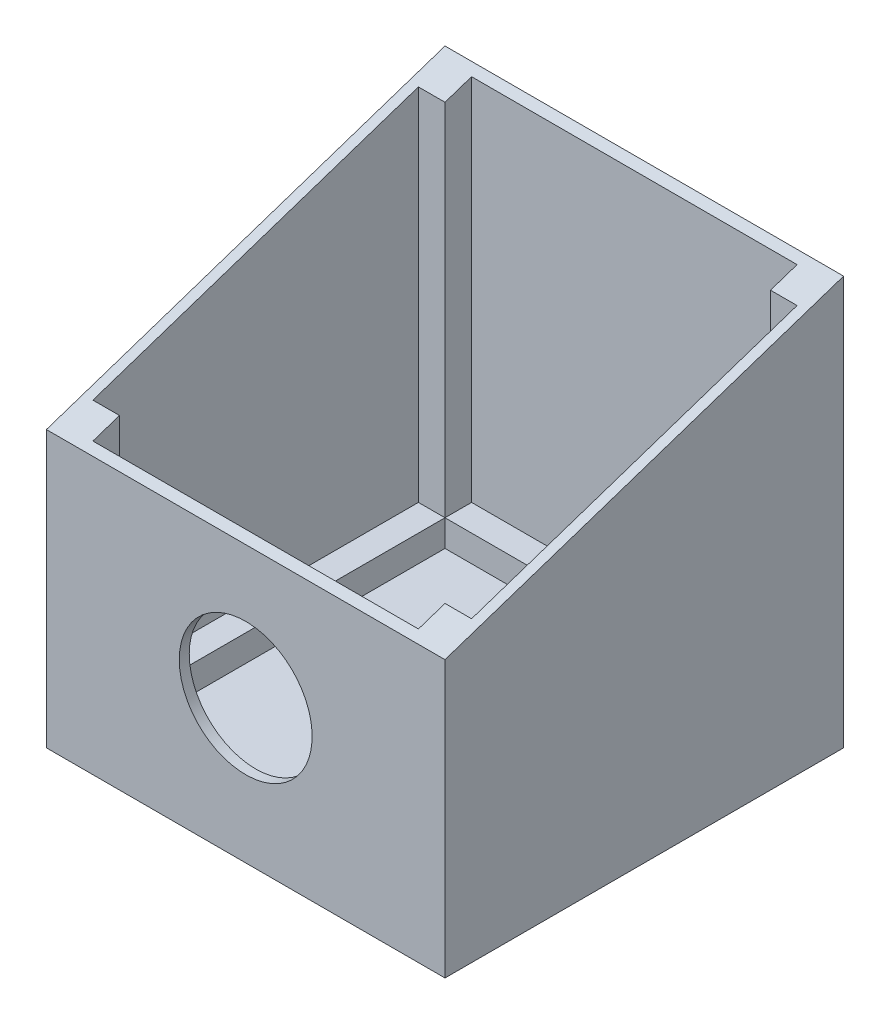
SolidWorks part; units mm, degrees
ref_plane "Alzado" through (0, 0, 0) normal (0, 0, 1) x (1, 0, 0)
ref_plane "Planta" through (0, 0, 0) normal (0, 1, 0) x (1, 0, 0)
ref_plane "Vista lateral" through (0, 0, 0) normal (1, 0, 0) x (0, 0, -1)
sketch "Croquis1" plane through (0, 0, 0) normal (0, 1, 0) x (1, 0, 0)
  line L0 (-3, 117) -> (117, 117)
  line L1 (8, 0) -> (106, 0)
  line L2 (0, 8) -> (0, 106)
  line L3 (8, 114) -> (106, 114)
  line L4 (114, 8) -> (114, 106)
  line L5 (117, -3) -> (117, 117)
  line L6 (-3, -3) -> (117, -3)
  line L7 (-3, -3) -> (-3, 117)
  line L8 (0, 114) -> (114, 114) construction
  line L9 (0, 0) -> (0, 114) construction
  line L10 (114, 0) -> (114, 114) construction
  line L11 (0, 106) -> (8, 106)
  line L12 (8, 114) -> (8, 106)
  line L13 (0, 0) -> (114, 0) construction
  line L15 (114, 106) -> (106, 106)
  line L16 (106, 114) -> (106, 106)
  line L19 (0, 8) -> (8, 8)
  line L20 (8, 0) -> (8, 8)
  line L23 (114, 8) -> (106, 8)
  line L24 (106, 0) -> (106, 8)
  dimension "D4" = 8
  dimension "D3" = 3
extrude "Saliente-Extruir1" add sketch "Croquis1" along normal blind 120
sketch "Croquis2" plane through (0, 0, 0) normal (1, 0, 0) x (0, 0, -1)
  line L0 (117, 120) -> (-3, 80)
  line L1 (-3, 120) -> (-3, 0) construction
  line L2 (-3, 80) -> (-3, 120)
  line L3 (-3, 120) -> (117, 120)
  dimension "D1" = 80
extrude "Cortar-Extruir1" cut sketch "Croquis2" along normal blind 120 and the other way blind 120
sketch "Croquis3" plane through (0, 0, 0) normal (0, 0, 1) x (1, 0, 0)
  circle A0 centre (57, 40) radius 20
extrude "Cortar-Extruir2" cut sketch "Croquis3" along normal blind 120
sketch "Croquis4" plane through (0, 0, 0) normal (0, 1, 0) x (1, 0, 0)
  line L0 (8, 106) -> (8, 8)
  line L1 (8, 8) -> (106, 8)
  line L2 (106, 8) -> (106, 106)
  line L3 (106, 106) -> (8, 106)
  line L9 (117, 117) -> (-3, 117)
  line L10 (117, -3) -> (117, 117)
  line L11 (-3, -3) -> (117, -3)
  line L12 (-3, 117) -> (-3, -3)
  line L13 (117, 117) -> (-3, 117)
  line L14 (117, -3) -> (117, 117)
  line L15 (-3, -3) -> (117, -3)
  line L16 (-3, 117) -> (-3, -3)
  line L25 (8, 0) -> (106, 0)
  line L26 (106, 0) -> (106, 8)
  line L27 (106, 8) -> (114, 8)
  line L28 (114, 8) -> (114, 106)
  line L29 (114, 106) -> (106, 106)
  line L30 (106, 106) -> (106, 114)
  line L31 (106, 114) -> (8, 114)
  line L32 (8, 114) -> (8, 106)
  line L33 (8, 106) -> (0, 106)
  line L34 (0, 106) -> (0, 8)
  line L35 (0, 8) -> (8, 8)
  line L36 (8, 8) -> (8, 0)
  line L37 (8, 0) -> (106, 0)
  line L38 (106, 0) -> (106, 8)
  line L39 (106, 8) -> (114, 8)
  line L40 (114, 8) -> (114, 106)
  line L41 (114, 106) -> (106, 106)
  line L42 (106, 106) -> (106, 114)
  line L43 (106, 114) -> (8, 114)
  line L44 (8, 114) -> (8, 106)
  line L45 (8, 106) -> (0, 106)
  line L46 (0, 106) -> (0, 8)
  line L47 (0, 8) -> (8, 8)
  line L48 (8, 8) -> (8, 0)
  dimension "D1" = 0
  dimension "D2" = 0
extrude "Saliente-Extruir2" add sketch "Croquis4" against normal blind 3 contours L13 L16 L15 L14
extrude "Saliente-Extruir3" add sketch "Croquis4<3>" along normal blind 8 contours L43 L44 L3 L42 | L40 L41 L2 L39 | L1 L48 L37 L38 | L46 L47 L0 L45 region at (57, 0, -110) region at (4, 0, -57) region at (57, 0, -4) region at (110, 0, -57)
sketch "Croquis4<3>" plane through (0, 0, 0) normal (0, 1, 0) x (1, 0, 0) same geometry as "Croquis4"
